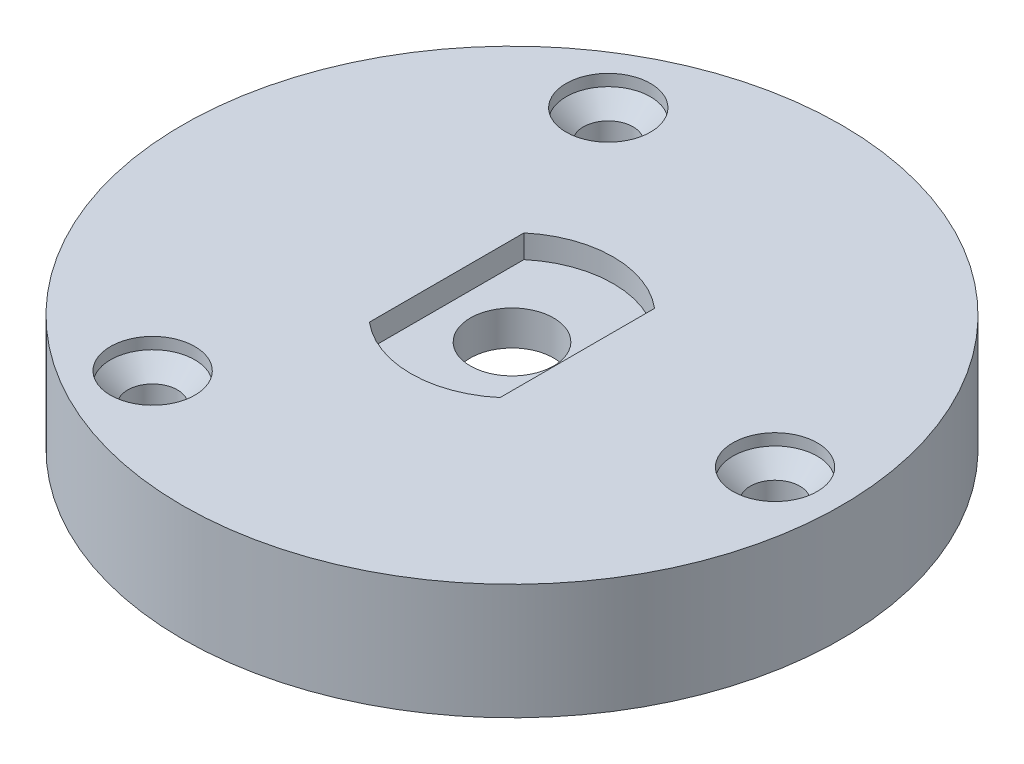
SolidWorks part; units mm, degrees
ref_plane "Спереди" through (0, 0, 0) normal (0, 0, 1) x (1, 0, 0)
ref_plane "Сверху" through (0, 0, 0) normal (0, 1, 0) x (1, 0, 0)
ref_plane "Справа" through (0, 0, 0) normal (1, 0, 0) x (0, 0, -1)
sketch "Основа" plane through (0, 0, 0) normal (0, 0, 1) x (1, 0, 0)
  line L0 (0, 24.7868) -> (0, -16.1363) construction
  line L1 (21.3873, 0) -> (-30.7086, 0) construction
  line L4 (3.6, 10) -> (28.5, 10)
  line L5 (28.5, 10) -> (28.5, 0)
  line L6 (28.5, 0) -> (17.15, 0)
  line L7 (17.15, 0) -> (17.15, 5)
  line L8 (17.15, 5) -> (3.6, 5)
  line L9 (3.6, 5) -> (3.6, 10)
  dimension "D2" = 17.15
  dimension "D1" = 28.5
  dimension "D3" = 10
  dimension "D4" = 5
  dimension "D5" = 3.6
revolve "Повернуть1" add sketch "Основа" angle 360 about L0
sketch "Посадка под резистор" plane through (0, 10, 0) normal (0, 1, 0) x (1, 0, 0)
  line L0 (-0.92, -7.2) -> (0.92, -7.2)
  line L1 (1.5, -7.78) -> (1.5, -8.0822)
  line L2 (-1.5, -7.78) -> (-1.5, -8.0822)
  line L3 (5.65, 6.6813) -> (5.65, -6.6813)
  line L4 (-5.65, 6.6813) -> (-5.65, -6.6813)
  arc A0 (-0.9471, -8.6986) -> (0.9471, -8.6986) centre (0, 0) ccw
  arc A1 (0.9471, -8.6986) -> (1.5, -8.0822) centre (0.88, -8.0822) ccw
  arc A2 (-0.9471, -8.6986) -> (-1.5, -8.0822) centre (-0.88, -8.0822) cw
  arc A3 (1.5, -7.78) -> (0.92, -7.2) centre (0.92, -7.78) ccw
  arc A4 (-1.5, -7.78) -> (-0.92, -7.2) centre (-0.92, -7.78) cw
  arc A5 (-5.65, -6.6813) -> (5.65, -6.6813) centre (0, 0) ccw
  circle A6 centre (0, 0) radius 3.6
  arc A7 (5.65, 6.6813) -> (-5.65, 6.6813) centre (0, 0) ccw
  point P7 (0, -7.2)
  point P13 (1.5, -7.2)
  point P16 (-1.5, -7.2)
  point P17 (5.65, 0)
  point P23 (0, 8.75)
  circle M3 centre (0, 0) radius 3.6
  dimension "D1" = 7.2
  dimension "D2" = 17.5
  dimension "D4" = 0.62
  dimension "D5" = 0.58
  dimension "D8" = 7.2
  dimension "D3" = 3
  dimension "D6" = 11.3
extrude "Выемка под резистор" cut sketch "Посадка под резистор" against normal blind 2 contours L3 A7 L4 A5 A2 L2 A4 L0 A3 L1 A1 M3 | A4 L2 A2 A0 A1 L1 A3 L0 region at (-1.4771, 10, 7.2229) region at (0, 10, 7.959)
extrude "Под пенек резистора" cut sketch "Эскиз2<3>" against normal blind 4 contours A4 L2 A2 A0 A1 L1 A3 L0 region at (0, 10, 7.959)
sketch "Эскиз2<3>" plane through (0, 10, 0) normal (0, 1, 0) x (1, 0, 0) same geometry as "Посадка под резистор"
sketch "Отверстия под болты" plane through (0, 10, 0) normal (0, 1, 0) x (1, 0, 0)
  line L0 (-22.75, 0) -> (22.75, 0) construction
  circle A0 centre (0, 0) radius 22.75
  circle A2 centre (22.75, 0) radius 2.15
  circle A3 centre (22.75, 0) radius 3.65
  circle A4 centre (-11.375, -19.7021) radius 2.15
  circle A5 centre (-11.375, -19.7021) radius 3.65
  circle A6 centre (-11.375, 19.7021) radius 2.15
  circle A7 centre (-11.375, 19.7021) radius 3.65
  point P16 (0, 0)
  dimension "D1" = 45.5
  dimension "D2" = 7.3
  dimension "D3" = 4.3
  dimension "D5" = 120
  dimension "D4" = 120
extrude "Отверстия" cut sketch "Отверстия под болты" against normal through all contours A0 A6 | A0 A6 | A0 A4 | A0 A4 | A0 A2 | L0 A2 A0 | A2 L0 A0 region at (21.8195, 10, -0.8982) region at (21.8195, 10, 0.8982) region at (-11.822, 10, -20.4763) region at (-10.9097, 10, -18.8962) region at (-10.9097, 10, 18.8962) region at (-11.822, 10, 20.4763) region at (23.6439, 10, 0)
extrude "Под шляпки" cut sketch "Эскиз3<5>" against normal blind 0.5 contours A0 A7 A6 | A0 A7 A6 | A0 A3 A2 | A3 L0 A2 A0 | L0 A3 A0 A2 | A0 A5 A4 | A0 A5 A4 region at (20.7853, 10, -1.8381) region at (20.7853, 10, 1.8381) region at (-13.155, 10, -22.7851) region at (-13.738, 10, -18.0275) region at (-10.3147, 10, 16.2979) region at (-13.8438, 10, 18.1663) region at (25.169, 10, -2.6215)
sketch "Эскиз3<5>" plane through (0, 10, 0) normal (0, 1, 0) x (1, 0, 0) same geometry as "Отверстия под болты"
chamfer "Фаска под шляпки" distance 2 angle 45 3 edges at (-11.375, 9.5, -17.5521) (22.75, 9.5, 2.15) (-11.375, 9.5, 21.8521)
